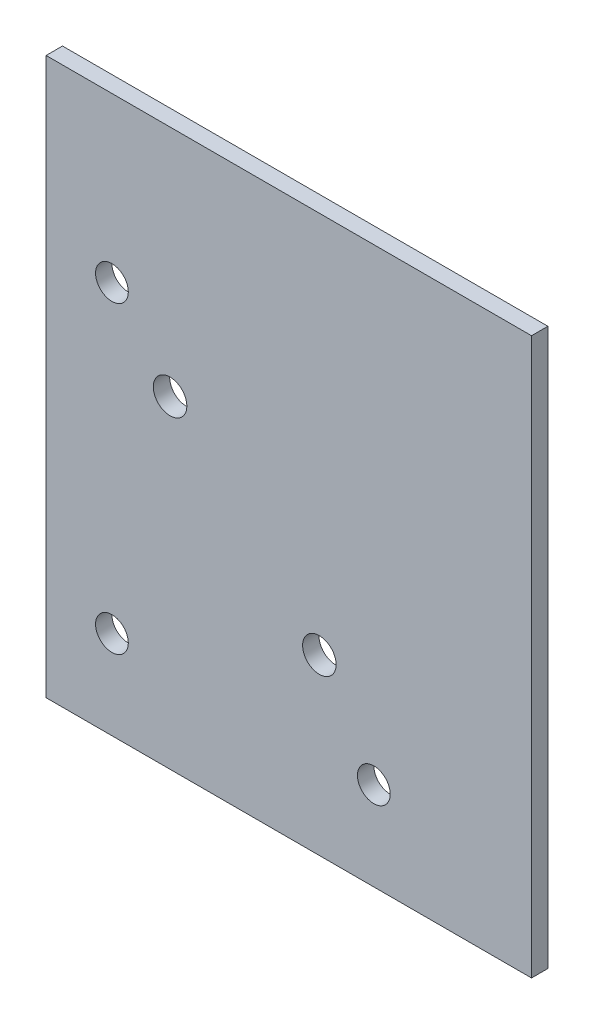
SolidWorks part; units mm, degrees
ref_plane "Front Plane" through (0, 0, 0) normal (0, 0, 1) x (1, 0, 0)
ref_plane "Top Plane" through (0, 0, 0) normal (0, 1, 0) x (1, 0, 0)
ref_plane "Right Plane" through (0, 0, 0) normal (1, 0, 0) x (0, 0, -1)
sketch "Sketch1" plane through (0, 0, 0) normal (0, 0, 1) x (1, 0, 0)
  line L1 (5.1833, 100.7604) -> (-88.9667, 100.7604)
  line L2 (5.1833, 100.7604) -> (5.1833, 208.6503)
  line L3 (5.1833, 208.6503) -> (-88.9667, 208.6503)
  line L4 (-88.9667, 100.7604) -> (-88.9667, 208.6503)
  line L5 (-23.2675, 150.6967) -> (-48.6675, 150.6967) construction
  line L6 (-48.6675, 201.4967) -> (-48.6675, 150.6967) construction
  circle A3 centre (-76.2, 117.9286) radius 3.175
  circle A4 centre (-25.4, 117.9286) radius 3.175
  circle A5 centre (-76.2, 176.8929) radius 3.175
  circle A6 centre (-64.9235, 163.3967) radius 3.2512
  circle A7 centre (-35.9675, 134.4407) radius 3.2512
  dimension "D1" = 6.5024
  dimension "D2" = 16.256
  dimension "D3" = 12.7
  dimension "D4" = 16.256
  dimension "D5" = 12.7
extrude "Boss-Extrude1" add sketch "Sketch1" along normal blind 3.175
equation "\"80/20 to Center Hole\"= .64in"
equation "\"80/20 from Edge\"= 0.5in"
equation "\"D5@Sketch1\"=\"80/20 from Edge\""
equation "\"D4@Sketch1\"=\"80/20 to Center Hole\""
equation "\"D2@Sketch1\"=\"80/20 to Center Hole\""
equation "\"D3@Sketch1\"=\"80/20 from Edge\""
